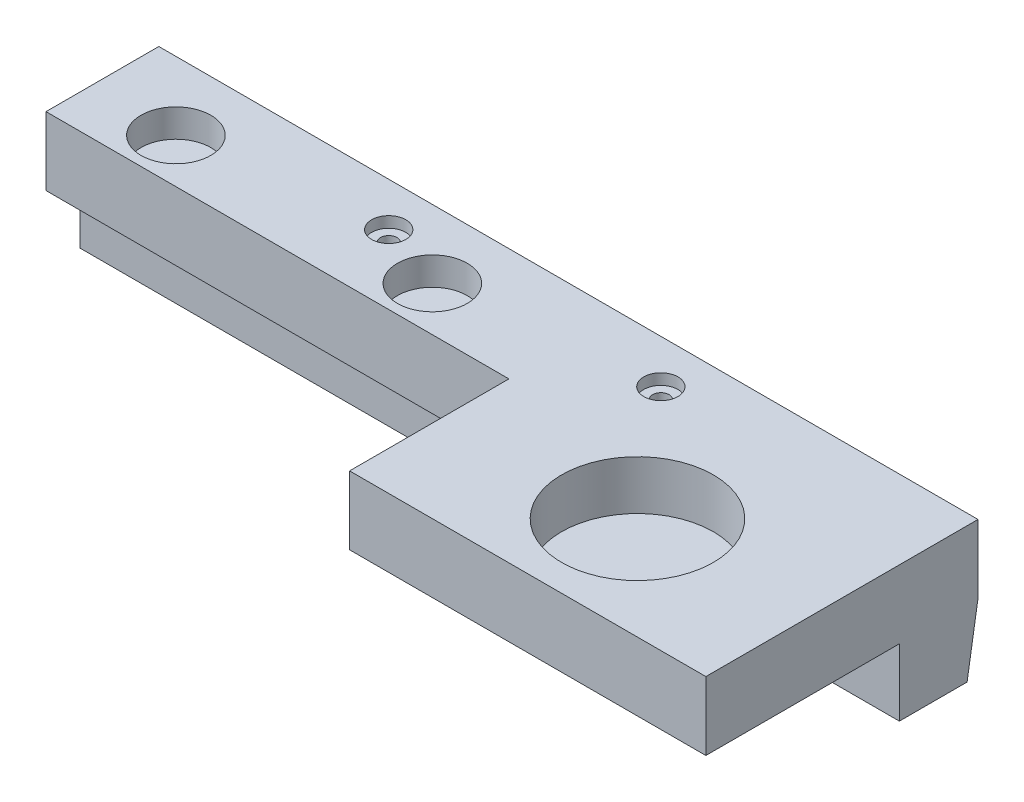
SolidWorks part; units mm, degrees
ref_plane "Płaszczyzna przednia" through (0, 0, 0) normal (0, 0, 1) x (1, 0, 0)
ref_plane "Płaszczyzna górna" through (0, 0, 0) normal (0, 1, 0) x (1, 0, 0)
ref_plane "Płaszczyzna prawa" through (0, 0, 0) normal (1, 0, 0) x (0, 0, -1)
sketch "Szkic1" plane through (0, 0, 0) normal (0, 0, 1) x (1, 0, 0)
  line L1 (-58.3066, 32.0248) -> (61.4934, 32.0248)
  line L2 (-58.3066, 32.0248) -> (-58.3066, 22.0248)
  line L3 (-58.3066, 22.0248) -> (61.4934, 22.0248)
  line L4 (61.4934, 32.0248) -> (61.4934, 22.0248)
  dimension "D1" = 119.8
  dimension "D2" = 10
extrude "Dodanie-wyciągnięcie2" add sketch "Szkic1" along normal blind 38.3 contours L2 L3 L4 L1
sketch "Szkic21" plane through (0, 32.0248, 0) normal (0, 1, 0) x (1, 0, 0)
  line L0 (61.4934, -38.3) -> (61.4934, 0) construction
  line L1 (-58.3066, 0) -> (61.4934, 0)
  line L2 (-58.3066, 0) -> (-58.3066, -10)
  line L3 (-58.3066, -10) -> (61.4934, -10)
  line L4 (61.4934, 0) -> (61.4934, -10)
extrude "Dodanie-wyciągnięcie3" add sketch "Szkic21" along normal blind 9.8
sketch "Szkic22" plane through (0, 22.0248, 0) normal (0, -1, 0) x (1, 0, 0)
  line L0 (-58.3066, 4.88) -> (-18.3066, 4.88) construction
  line L1 (-58.3066, 38.3) -> (-58.3066, 0) construction
  line L2 (-18.3066, 4.88) -> (21.4934, 4.88) construction
  line L3 (21.4934, 4.88) -> (61.4934, 4.88) construction
  line L4 (61.4934, 38.3) -> (61.4934, 0) construction
  line L5 (1.9729, 4.88) -> (1.9729, 0) construction
  line L6 (-58.3066, 0) -> (61.4934, 0) construction
hole_wizard "Pogłębienie walcowe pod M2 wkręt do części metalowych z łbem stożkowym ściętym2" positions "Szkic23" profile "Szkic24" counterbore size "M2" standard "Ansi Metric" end condition through all
sketch "Szkic23" plane through (0, 22.0248, 0) normal (0, -1, 0) x (-1, 0, 0)
  point P0 (-21.4934, -4.88)
  point P3 (18.3066, -4.88)
sketch "Szkic24" plane through (21.4934, 22.0248, 4.88) normal (1, 0, 0) x (0, 0, -1)
  line L0 (0, 0) -> (0, 19.8)
  line L1 (0, 19.8) -> (1.2, 19.8)
  line L3 (1.2, 19.8) -> (1.2, 1.6)
  line L4 (1.2, 1.6) -> (2.5, 1.6)
  line L5 (2.5, 1.6) -> (2.5, 0)
  line L7 (2.5, 0) -> (0, 0)
  line L11 (0, -6.35) -> (0, 107.95) construction
  dimension "Średnica otworu na wylot" = 2.4
  dimension "Głębokość otworu na wylot" = 19.8
  dimension "Średnica pogłębienia walcowego" = 5
  dimension "Głębokość pogłębienia walcowego" = 1.6
sketch "Szkic28" plane through (0, 22.0248, 0) normal (0, -1, 0) x (1, 0, 0)
  line L0 (36.4934, 0) -> (36.4934, 23.3) construction
  line L1 (-58.3066, 0) -> (61.4934, 0) construction
  line L2 (36.4934, 23.3) -> (61.4934, 23.3) construction
  line L3 (61.4934, 38.3) -> (61.4934, 0) construction
  line L4 (-58.3066, 38.3) -> (61.4934, 38.3) construction
  circle A0 centre (36.4934, 23.3) radius 11.1
  dimension "D1" = 15
extrude "Wytnij-wyciągnięcie1" cut sketch "Szkic28" against normal blind 7.2
sketch "Szkic31" plane through (61.4934, 0, 0) normal (1, 0, 0) x (0, 0, -1)
  line L0 (-10, 32.0248) -> (-10, 71.9248)
  line L2 (0, 41.2325) -> (0, 32.0248)
  line L6 (0, 41.8248) -> (0, 22.0248) construction
  line L8 (0, 32.0248) -> (1.5, 32.0248)
  line L10 (-10, 32.0248) -> (1.5, 32.0248)
  line L12 (-10, 71.9248) -> (-5, 71.9248)
  line L13 (-5, 71.9248) -> (1.5, 32.0248)
  line L14 (-0.4105, 43.7521) -> (0.2752, 39.543)
  line L15 (0.2752, 39.543) -> (3.3905, 40.0505)
  line L16 (3.3905, 40.0505) -> (-0.4105, 43.7521)
  line M5 (0, 22.0248) -> (0, 41.8248)
  line M6 (0, 41.8248) -> (-10, 41.8248)
extrude "Wytnij-wyciągnięcie4" cut sketch "Szkic31" against normal blind 124.8 contours L13 M6 M5 region at (61.4934, 41.6274, 0.0322)
extrude "Dodanie-wyciągnięcie5" add sketch "Szkic31<5>" against normal blind 119.8 contours L13 L8 M5 region at (61.4934, 35.0941, -0.5)
sketch "Szkic31<5>" plane through (61.4934, 0, 0) normal (1, 0, 0) x (0, 0, -1) same geometry as "Szkic31"
sketch "Szkic34" plane through (0, 0, 0) normal (0, 0, -1) x (-1, 0, 0)
  line L1 (-61.4934, 32.0248) -> (58.3066, 32.0248)
  line L2 (-61.4934, 32.0248) -> (-61.4934, 22.0248)
  line L3 (-61.4934, 22.0248) -> (58.3066, 22.0248)
  line L4 (58.3066, 32.0248) -> (58.3066, 22.0248)
extrude "Dodanie-wyciągnięcie6" add sketch "Szkic34" along normal blind 1.5
sketch "Szkic37" plane through (0, 32.0248, 0) normal (0, 1, 0) x (1, 0, 0)
  line L1 (61.4934, -38.3) -> (9.3934, -38.3)
  line L2 (61.4934, -38.3) -> (61.4934, -30)
  line L3 (61.4934, -30) -> (9.3934, -30)
  line L4 (9.3934, -38.3) -> (9.3934, -30)
mirror "Lustro2" about plane through (-58.3066, 22.0248, 38.3) normal (0, 1, 0) of bodies 125 144
move or copy body "Obiekt-Przenieś/Kopiuj1" bodies to move or copy 146 copy no translate (0, -36.7663, 0) parameters "D1"=0, "D2"=36.7663, "D3"=0
delete or keep bodies "Obiekt-Usuń/zachowaj 1" type delete bodies bodies 125
sketch "Szkic38" plane through (0, 0, 38.3) normal (0, 0, 1) x (1, 0, 0)
  line L0 (-58.3066, -24.7414) -> (61.4934, -24.7414) construction
  line L1 (-58.3066, -14.7414) -> (9.3934, -14.7414)
  line L2 (-58.3066, -14.7414) -> (-58.3066, -24.7414)
  line L3 (-58.3066, -24.7414) -> (9.3934, -24.7414)
  line L4 (9.3934, -14.7414) -> (9.3934, -24.7414)
extrude "Wytnij-wyciągnięcie5" cut sketch "Szkic38" against normal blind 23.3
sketch "Szkic39" plane through (0, -14.7414, 0) normal (0, 1, 0) x (1, 0, 0)
  line L0 (-58.3066, -8.5) -> (-33.3066, -8.5) construction
  line L2 (-33.3066, -8.5) -> (-8.3066, -8.5) construction
  line L3 (61.4934, 1.5) -> (-58.3066, 1.5) construction
  circle A0 centre (-45.8066, -8.5) radius 5.1
  circle A1 centre (-8.3066, -8.5) radius 5.1
  dimension "D1" = 10
extrude "Wytnij-wyciągnięcie6" cut sketch "Szkic39" against normal blind 4.1
